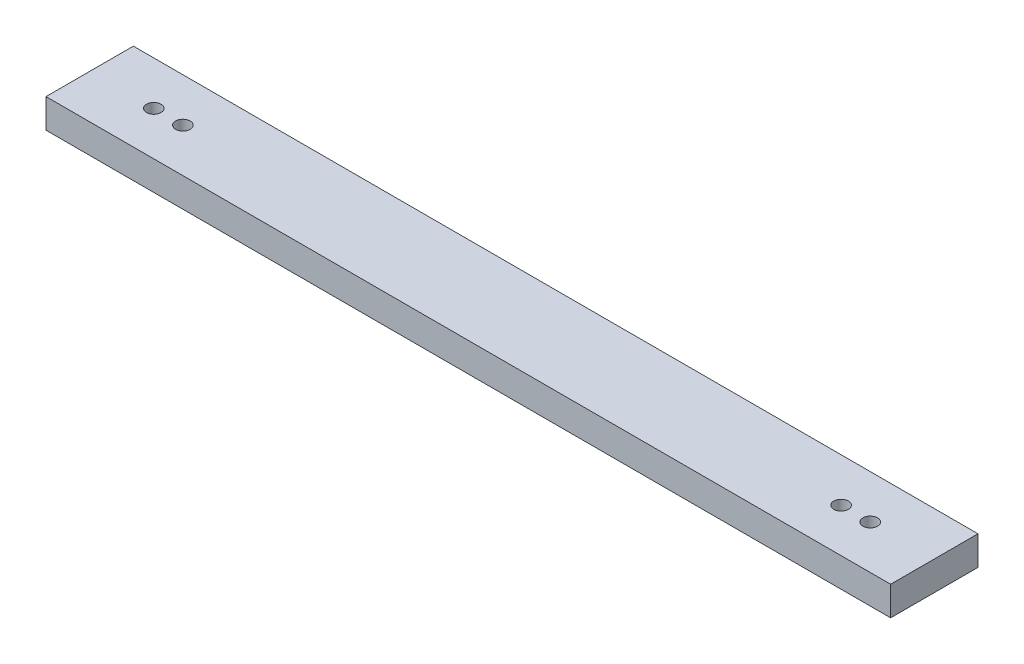
SolidWorks part; units mm, degrees
ref_plane "Front Plane" through (0, 0, 0) normal (0, 0, 1) x (1, 0, 0)
ref_plane "Top Plane" through (0, 0, 0) normal (0, 1, 0) x (1, 0, 0)
ref_plane "Right Plane" through (0, 0, 0) normal (1, 0, 0) x (0, 0, -1)
sketch "Sketch3" plane through (0, 0, 0) normal (0, 1, 0) x (1, 0, 0)
  line L1 (0, 80) -> (580, 80)
  line L2 (0, 80) -> (0, 20)
  line L3 (0, 20) -> (580, 20)
  line L4 (580, 80) -> (580, 20)
  dimension "D1" = 580
  dimension "D2" = 60
extrude "Boss-Extrude1" add sketch "Sketch3" along normal blind 20
sketch "Sketch4" plane through (0, 20, 0) normal (0, 1, 0) x (1, 0, 0)
  circle A0 centre (44, 50) radius 5
  circle A1 centre (64, 50) radius 5
  circle A2 centre (516, 50) radius 5
  circle A3 centre (536, 50) radius 5
  dimension "D1" = 10
  dimension "D3" = 10
  dimension "D4" = 10
  dimension "D5" = 10
  dimension "D2" = 20
extrude "Cut-Extrude1" cut sketch "Sketch4" against normal through all
